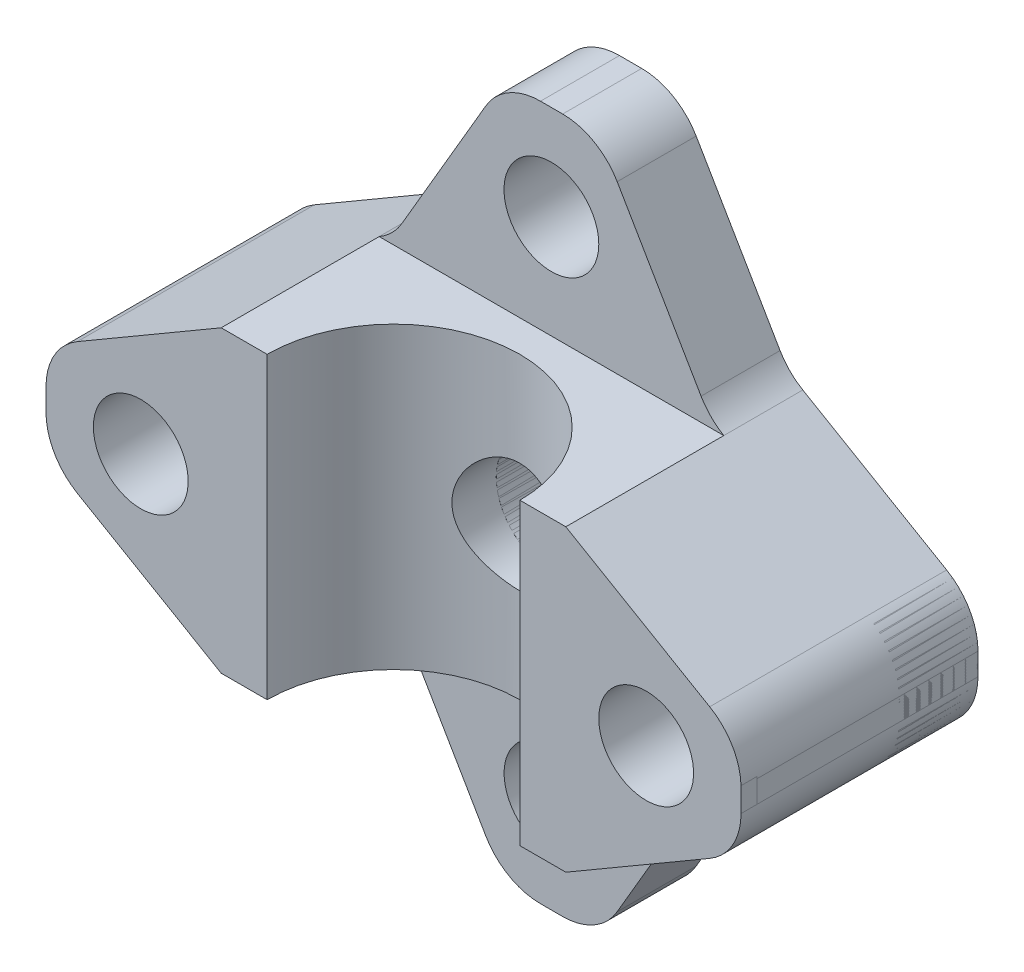
SolidWorks part; units mm, degrees
material "ABS"
ref_plane "Front Plane" through (0, 0, 0) normal (0, 0, 1) x (1, 0, 0)
ref_plane "Top Plane" through (0, 0, 0) normal (0, 1, 0) x (1, 0, 0)
ref_plane "Right Plane" through (0, 0, 0) normal (1, 0, 0) x (0, 0, -1)
sketch "Sketch1" plane through (0, 0, 0) normal (0, 0, 1) x (1, 0, 0)
  line L0 (0, 14.8318) -> (0, -14.8318)
  line L1 (-5, 14.8318) -> (-5, -14.8318)
  line L2 (5, 14.8318) -> (5, -14.8318)
  line L3 (-12.5, 0) -> (0, -12.5)
  line L4 (-12.5, 0) -> (0, 12.5)
  line L5 (0, -12.5) -> (12.5, 0)
  line L6 (0, 12.5) -> (12.5, 0)
  line L7 (-12.5, 0) -> (12.5, 0) construction
  line L8 (0, -12.5) -> (0, 12.5) construction
  line L9 (-10.9858, 11.0142) -> (11.0142, 10.9858)
  line L10 (-10.9858, 11.0142) -> (-11.0142, -10.9858)
  line L11 (11.0142, 10.9858) -> (10.9858, -11.0142)
  line L12 (-11.0142, -10.9858) -> (10.9858, -11.0142)
  line L13 (-10.9858, 11.0142) -> (10.9858, -11.0142) construction
  line L14 (11.0142, 10.9858) -> (-11.0142, -10.9858) construction
  circle A0 centre (0, 0) radius 8
  circle A1 centre (-8, 0) radius 1.5
  circle A2 centre (-0.0028, 8) radius 1.5
  circle A3 centre (7.9972, 0.0028) radius 1.5
  circle A4 centre (0, -7.9972) radius 1.5
  point P14 (-0.0014, 0.0014)
  point P15 (0, 0)
  dimension "D2" = 3
  dimension "D3" = 16
  dimension "D6" = 25
  dimension "D7" = 22
  dimension "D4" = 5
  dimension "D5" = 5
  dimension "D1" = 4
extrude "Boss-Extrude1" add sketch "Sketch1" along normal blind 2.5 contours A1 A0 L1 L4 L10 L3 | A2 L0 L9 L4 L1 A0 | A2 A0 L2 L6 L9 L0 | A3 A0 L2 L5 L11 L6 | A4 A0 L1 L3 L12 L0 | A4 L0 L12 L5 L2 A0 | A4 L0 A2 A0 L1 | A1 A0 L1 | A4 A0 L2 A2 L0 | A3 A0 L2 region at (2.3757, 8.8871, 0) region at (-2.3764, 8.8879, 0) region at (-5.1616, 6.8725, 0) region at (7.8867, 4.3848, 0) region at (-2.4899, 0, 0) region at (-6.0547, 0, 0) region at (6.0544, -0.0004, 0) region at (2.4898, 0.0008, 0) region at (-2.3756, -8.8873, 0) region at (2.3752, -8.8879, 0)
sketch "Sketch2" plane through (0, 0, 2.5) normal (0, 0, 1) x (1, 0, 0)
  line L4 (-5, -5) -> (5, 5) construction
  line L5 (5, -5) -> (-5, 5) construction
  line L6 (-5, 5) -> (-10.9981, 1.5019)
  line L7 (-5, -5) -> (5, -5)
  line L8 (-5, -5) -> (-5, 5)
  line L9 (-5, 5) -> (5, 5)
  line L10 (5, -5) -> (5, 5)
  line L11 (-5, -5) -> (5, 5) construction
  line L12 (-5, 5) -> (5, -5) construction
  line L13 (-5, 5) -> (-1.498, 11.002)
  line L14 (-1.498, 11.002) -> (1.5019, 10.9981)
  line L15 (1.5019, 10.9981) -> (5, 5)
  line L16 (5, 5) -> (11.002, 1.498)
  line L17 (-11.002, -1.498) -> (-5, -5)
  line L18 (-5, -5) -> (-1.5019, -10.9981)
  line L19 (1.498, -11.002) -> (5, -5)
  line L20 (10.9981, -1.5019) -> (5, -5)
  line L25 (1.498, -11.002) -> (10.9981, -1.5019)
  line L26 (10.9981, -1.5019) -> (11.002, 1.498)
  line L27 (11.002, 1.498) -> (1.5019, 10.9981)
  line L28 (1.5019, 10.9981) -> (-1.498, 11.002)
  line L29 (-1.498, 11.002) -> (-10.9981, 1.5019)
  line L30 (-10.9981, 1.5019) -> (-11.002, -1.498)
  line L31 (-11.002, -1.498) -> (-1.5019, -10.9981)
  line L32 (-1.5019, -10.9981) -> (1.498, -11.002)
  line L33 (1.498, -11.002) -> (10.9981, -1.5019)
  line L34 (10.9981, -1.5019) -> (11.002, 1.498)
  line L35 (11.002, 1.498) -> (1.5019, 10.9981)
  line L36 (1.5019, 10.9981) -> (-1.498, 11.002)
  line L37 (-1.498, 11.002) -> (-10.9981, 1.5019)
  line L38 (-10.9981, 1.5019) -> (-11.002, -1.498)
  line L39 (-11.002, -1.498) -> (-1.5019, -10.9981)
  line L40 (-1.5019, -10.9981) -> (1.498, -11.002)
  point P0 (0, 0)
  line M18 (1.498, -11.002) -> (10.9981, -1.5019)
  line M20 (11.002, 1.498) -> (1.5019, 10.9981)
  line M22 (-1.498, 11.002) -> (-10.9981, 1.5019)
  line M24 (-11.002, -1.498) -> (-1.5019, -10.9981)
  dimension "D1" = 10
  dimension "D2" = 0
extrude "Cut-Extrude1" cut sketch "Sketch2" against normal blind 2.5 contours L6 L13 M22 | L18 L17 M24 | L15 L16 M20 | L20 L19 M18 region at (-5.832, 5.8346, 2.5) region at (-5.8346, -5.832, 2.5) region at (5.8346, 5.832, 2.5) region at (5.832, -5.8346, 2.5)
sketch "Sketch3" plane through (0, 0, 2.5) normal (0, 0, 1) x (1, 0, 0)
  circle A0 centre (0, 0) radius 1.75
  dimension "D1" = 3.5
extrude "Cut-Extrude2" cut sketch "Sketch3" against normal blind 2.5
fillet "Fillet1" radius 2 12 edges at (-10.9981, 1.5019, 1.25) (-5, 5, 1.25) (-1.498, 11.002, 1.25) (1.5019, 10.9981, 1.25) (5, 5, 1.25) (11.002, 1.498, 1.25) (10.9981, -1.5019, 1.25) (5, -5, 1.25) (1.498, -11.002, 1.25) (-1.5019, -10.9981, 1.25) (-5, -5, 1.25) (-11.002, -1.498, 1.25)
sketch "Sketch4" plane through (0, 0, 0) normal (0, 0, 1) x (1, 0, 0)
  line L0 (-5.4546, 4.7349) -> (5.4546, 4.7348)
  line L1 (-5.4546, -4.7348) -> (5.4546, -4.7349)
  line L12 (-5.4546, 4.7349) -> (-10.0071, 2.0798)
  line L13 (-10.9996, 0.3548) -> (-11.0005, -0.3477)
  line L14 (-10.0084, -2.0778) -> (-5.4546, -4.7348)
  line L15 (-4.7349, -5.4546) -> (-2.0798, -10.0071)
  line L16 (-0.3548, -10.9996) -> (0.3477, -11.0005)
  line L17 (2.0778, -10.0084) -> (4.7348, -5.4546)
  line L18 (5.4546, -4.7349) -> (10.0071, -2.0798)
  line L19 (10.9996, -0.3548) -> (11.0005, 0.3477)
  line L20 (10.0084, 2.0778) -> (5.4546, 4.7348)
  line L21 (4.7349, 5.4546) -> (2.0798, 10.0071)
  line L22 (0.3548, 10.9996) -> (-0.3477, 11.0005)
  line L23 (-2.0778, 10.0084) -> (-4.7348, 5.4546)
  line L24 (-5.4546, 4.7349) -> (-10.0071, 2.0798)
  line L25 (-10.9996, 0.3548) -> (-11.0005, -0.3477)
  line L26 (-10.0084, -2.0778) -> (-5.4546, -4.7348)
  line L27 (-4.7349, -5.4546) -> (-2.0798, -10.0071)
  line L28 (-0.3548, -10.9996) -> (0.3477, -11.0005)
  line L29 (2.0778, -10.0084) -> (4.7348, -5.4546)
  line L30 (5.4546, -4.7349) -> (10.0071, -2.0798)
  line L31 (10.9996, -0.3548) -> (11.0005, 0.3477)
  line L32 (10.0084, 2.0778) -> (5.4546, 4.7348)
  line L33 (4.7349, 5.4546) -> (2.0798, 10.0071)
  line L34 (0.3548, 10.9996) -> (-0.3477, 11.0005)
  line L35 (-2.0778, 10.0084) -> (-4.7348, 5.4546)
  circle A0 centre (-8, 0) radius 1.5 construction
  circle A1 centre (0, 0) radius 1.75
  circle A2 centre (0, 0) radius 1.75
  circle A3 centre (7.9972, 0.0028) radius 1.5
  circle A4 centre (7.9972, 0.0028) radius 1.5
  circle A5 centre (-0.0028, 8) radius 1.5
  circle A6 centre (-0.0028, 8) radius 1.5
  circle A7 centre (0, -7.9972) radius 1.5
  circle A8 centre (0, -7.9972) radius 1.5
  circle A9 centre (-8, 0) radius 1.5
  arc A12 (-10.0071, 2.0798) -> (-10.9996, 0.3548) centre (-8.9996, 0.3522) ccw
  arc A13 (-11.0005, -0.3477) -> (-10.0084, -2.0778) centre (-9.0005, -0.3503) ccw
  arc A14 (-4.7349, -5.4546) -> (-5.4546, -4.7348) centre (-6.4625, -6.4622) ccw
  arc A15 (-2.0798, -10.0071) -> (-0.3548, -10.9996) centre (-0.3522, -8.9996) ccw
  arc A16 (0.3477, -11.0005) -> (2.0778, -10.0084) centre (0.3503, -9.0005) ccw
  arc A17 (5.4546, -4.7349) -> (4.7348, -5.4546) centre (6.4622, -6.4625) ccw
  arc A18 (10.0071, -2.0798) -> (10.9996, -0.3548) centre (8.9996, -0.3522) ccw
  arc A19 (11.0005, 0.3477) -> (10.0084, 2.0778) centre (9.0005, 0.3503) ccw
  arc A20 (4.7349, 5.4546) -> (5.4546, 4.7348) centre (6.4625, 6.4622) ccw
  arc A21 (2.0798, 10.0071) -> (0.3548, 10.9996) centre (0.3522, 8.9996) ccw
  arc A22 (-0.3477, 11.0005) -> (-2.0778, 10.0084) centre (-0.3503, 9.0005) ccw
  arc A23 (-5.4546, 4.7349) -> (-4.7348, 5.4546) centre (-6.4622, 6.4625) ccw
  arc A24 (-10.0071, 2.0798) -> (-10.9996, 0.3548) centre (-8.9996, 0.3522) ccw
  arc A25 (-11.0005, -0.3477) -> (-10.0084, -2.0778) centre (-9.0005, -0.3503) ccw
  arc A26 (-4.7349, -5.4546) -> (-5.4546, -4.7348) centre (-6.4625, -6.4622) ccw
  arc A27 (-2.0798, -10.0071) -> (-0.3548, -10.9996) centre (-0.3522, -8.9996) ccw
  arc A28 (0.3477, -11.0005) -> (2.0778, -10.0084) centre (0.3503, -9.0005) ccw
  arc A29 (5.4546, -4.7349) -> (4.7348, -5.4546) centre (6.4622, -6.4625) ccw
  arc A30 (10.0071, -2.0798) -> (10.9996, -0.3548) centre (8.9996, -0.3522) ccw
  arc A31 (11.0005, 0.3477) -> (10.0084, 2.0778) centre (9.0005, 0.3503) ccw
  arc A32 (4.7349, 5.4546) -> (5.4546, 4.7348) centre (6.4625, 6.4622) ccw
  arc A33 (2.0798, 10.0071) -> (0.3548, 10.9996) centre (0.3522, 8.9996) ccw
  arc A34 (-0.3477, 11.0005) -> (-2.0778, 10.0084) centre (-0.3503, 9.0005) ccw
  arc A35 (-5.4546, 4.7349) -> (-4.7348, 5.4546) centre (-6.4622, 6.4625) ccw
  dimension "D1" = 0
  dimension "D2" = 0
  dimension "D3" = 0
  dimension "D4" = 0
  dimension "D5" = 0
extrude "Boss-Extrude2" add sketch "Sketch4" along normal blind 15 separate body contours L31 A31 L32 L0 L24 A24 L25 A25 L26 L1 L30 A30 A9 A4 A2 region at (0, 4.4953, 0)
sketch "Sketch5" plane through (0, -4.7348, 0) normal (0, -1, 0) x (1, 0, 0)
  line L0 (-11.0005, 7.5) -> (10.9996, 7.5)
  line L1 (-11.0005, 15) -> (-11.0005, 0) construction
  line L2 (10.9996, 15) -> (10.9996, 0) construction
  line L3 (-11.0005, 7) -> (10.9996, 7)
  line L4 (-11.0005, 8) -> (10.9996, 8)
  line L5 (10.9996, 8) -> (10.9996, 7)
  line L6 (-11.0005, 8) -> (-11.0005, 7)
  line L7 (10.0071, 0) -> (10.9996, 0) construction
  line L8 (10.9996, 0) -> (10.9996, 15) construction
  line L9 (10.9996, 15) -> (10.0071, 15) construction
  line L10 (5.4547, 0) -> (10.0071, 0) construction
  line L11 (-11.0005, 0) -> (-10.0084, 0)
  line L12 (-10.0084, 0) -> (-10.0084, 15)
  line L13 (-10.0084, 15) -> (-11.0005, 15)
  line L14 (-11.0005, 15) -> (-11.0005, 0)
  line L15 (-11.0005, 0) -> (-10.0084, 0)
  line L16 (-10.0084, 0) -> (-10.0084, 15)
  line L17 (-10.0084, 15) -> (-11.0005, 15)
  line L18 (-11.0005, 15) -> (-11.0005, 0)
  line L19 (10.0071, 15) -> (5.4547, 15) construction
  line L20 (-5.4546, 0) -> (5.4547, 0) construction
  line L21 (5.4547, 15) -> (-5.4546, 15) construction
  line L22 (-10.0084, 0) -> (-5.4546, 0) construction
  line L23 (-5.4546, 15) -> (-10.0084, 15) construction
  line L24 (-10.0084, 15) -> (-10.0084, 0) construction
  line L25 (10.0071, 0) -> (10.9996, 0)
  line L26 (10.9996, 0) -> (10.9996, 15)
  line L27 (10.9996, 15) -> (10.0071, 15)
  line L28 (5.4547, 0) -> (10.0071, 0)
  line L29 (10.0071, 15) -> (5.4547, 15)
  line L30 (-5.4546, 0) -> (5.4547, 0)
  line L31 (5.4547, 15) -> (-5.4546, 15)
  line L32 (-10.0084, 0) -> (-5.4546, 0)
  line L33 (-5.4546, 15) -> (-10.0084, 15)
  line L34 (-10.0084, 15) -> (-10.0084, 0)
  line L36 (-11.0005, 7) -> (12.2639, 7)
  line L37 (-11.0005, 7) -> (-11.0005, 16)
  line L38 (-11.0005, 16) -> (12.2639, 16)
  line L39 (12.2639, 7) -> (12.2639, 16)
  circle A0 centre (-0.0005, 7.5) radius 4
  line M8 (5.4547, 0) -> (5.4547, 15)
  line M9 (5.4547, 15) -> (-5.4546, 15)
  line M10 (-5.4546, 15) -> (-5.4546, 0)
  dimension "D1" = 8
  dimension "D5" = 9
  dimension "D2" = 0.5
  dimension "D3" = 0.5
  dimension "D4" = 0
extrude "Cut-Extrude3" cut sketch "Sketch5" against normal blind 10 contours L36 L39 L38 L37 L17 L33 L29 L27 L26 L5 M9 | L27 L29 L4 L26 M8 | A0 L4 M8 M9 M10 | L33 L16 L4 M10 | L17 L18 L4 L16 | L16 L0 L4 M10 | L0 L16 L4 L6 | L0 A0 L4 | A0 L4 L0 M10 | A0 L0 L4 M8 | L5 L4 L0 M8 | L4 A0 | L36 A0 | L0 A0 L36 region at (-10.5045, -4.7347, 7.75) region at (-7.7315, -4.7347, 7.75) region at (-10.5045, -4.7347, 11.5) region at (-4.7223, -4.7348, 7.7509) region at (-7.7315, -4.7347, 11.5) region at (-10.7511, -4.7347, 15.5) region at (-0.0005, -4.7348, 7.7497) region at (-0.0005, -4.7348, 7.2503) region at (0.0002, -4.7348, 12.2769) region at (4.7218, -4.7348, 7.7509) region at (-0.0005, -4.7348, 9.4709) region at (-0.0005, -4.7348, 5.5291) region at (8.2271, -4.7349, 7.75) region at (8.2271, -4.7349, 11.5)
